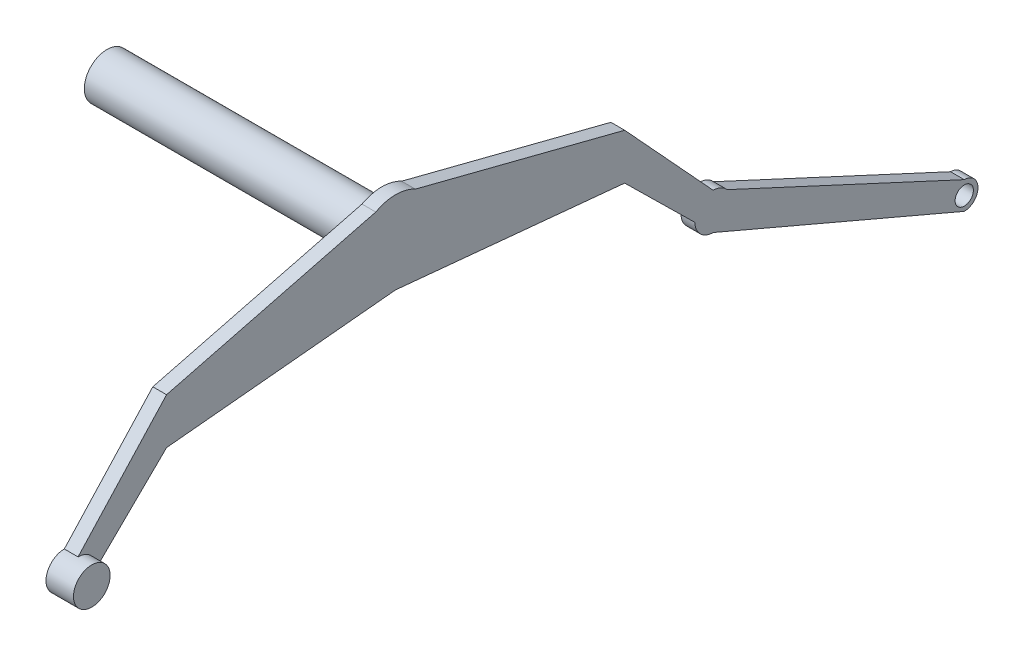
SolidWorks part; units mm, degrees
ref_plane "Front Plane" through (0, 0, 0) normal (0, 0, 1) x (1, 0, 0)
ref_plane "Top Plane" through (0, 0, 0) normal (0, 1, 0) x (1, 0, 0)
ref_plane "Right Plane" through (0, 0, 0) normal (1, 0, 0) x (0, 0, -1)
sketch "Sketch1" plane through (0, 0, 0) normal (1, 0, 0) x (0, 0, -1)
  line L0 (0, 0) -> (-500, -88.1635) construction
  line L1 (0, 90) -> (0, -49910) construction
  line L2 (-500, -88.1635) -> (-693.1378, -288.1635) construction
  line L3 (-500, -38.1635) -> (-500, -138.1635) construction
  line L4 (-693.1378, -248.1635) -> (-500, -38.1635)
  line L5 (-500, -38.1635) -> (0, 90)
  line L6 (-693.1378, -328.1635) -> (-500, -138.1635)
  line L7 (-500, -138.1635) -> (0, -90)
  line L8 (693.1378, -248.1635) -> (693.1378, -328.1635) construction
  line L9 (500, -138.1635) -> (0, -90)
  line L10 (500, -38.1635) -> (0, 90)
  line L11 (693.1378, -328.1635) -> (500, -138.1635)
  line L12 (693.1378, -248.1635) -> (500, -38.1635)
  line L13 (693.1378, -288.1635) -> (693.1378, -532.2035) construction
  line L14 (693.1378, -288.1635) -> (1241.2606, -532.2035) construction
  line L15 (693.1378, -328.1635) -> (1241.2606, -562.2035)
  line L16 (693.1378, -248.1635) -> (1241.2606, -502.2035)
  circle A0 centre (0, 0) radius 49.5
  circle A1 centre (0, 0) radius 90
  circle A2 centre (-693.1378, -288.1635) radius 40
  circle A3 centre (693.1378, -288.1635) radius 40
  circle A4 centre (1241.2606, -532.2035) radius 20
  circle A5 centre (1241.2606, -532.2035) radius 30
  dimension "D1" = 99
  dimension "D2" = 180
  dimension "D7" = 80
  dimension "D11" = 40
  dimension "D12" = 60
  dimension "D3" = 500
  dimension "D4" = 80
  dimension "D5" = 144
  dimension "D6" = 200
  dimension "D8" = 100
  dimension "D9" = 244.04
  dimension "D10" = 66
extrude "Boss-Extrude1" add sketch "Sketch1" along normal blind 30 contours A2 L6 L7 A1 L5 L4 | L11 A3 L12 L10 A1 L9 | A5 L16 A3 L15 | A3 L11 L16 | A3 L11 | A5 L15 A4 | A3 | A1 | A2 region at (0, -74.3749, 333.7474) region at (0, -74.3749, -333.7474) region at (0, -286.4715, -695.1351) region at (0, -311.81, -669.8754) region at (0, -407.3992, -960.3799) region at (0, -520.7561, -1214.4508)
extrude "Boss-Extrude2" add sketch "Sketch1<3>" along normal blind 60 contours L6 A2 | L6 A2 region at (0, -285.8744, 695.3896) region at (0, -311.81, 669.8754)
sketch "Sketch1<3>" plane through (0, 0, 0) normal (1, 0, 0) x (0, 0, -1) same geometry as "Sketch1"
extrude "Boss-Extrude3" add sketch "Sketch1<4>" against normal blind 600 contours A0 region at (0, 0, 0)
sketch "Sketch1<4>" plane through (0, 0, 0) normal (1, 0, 0) x (0, 0, -1) same geometry as "Sketch1"
